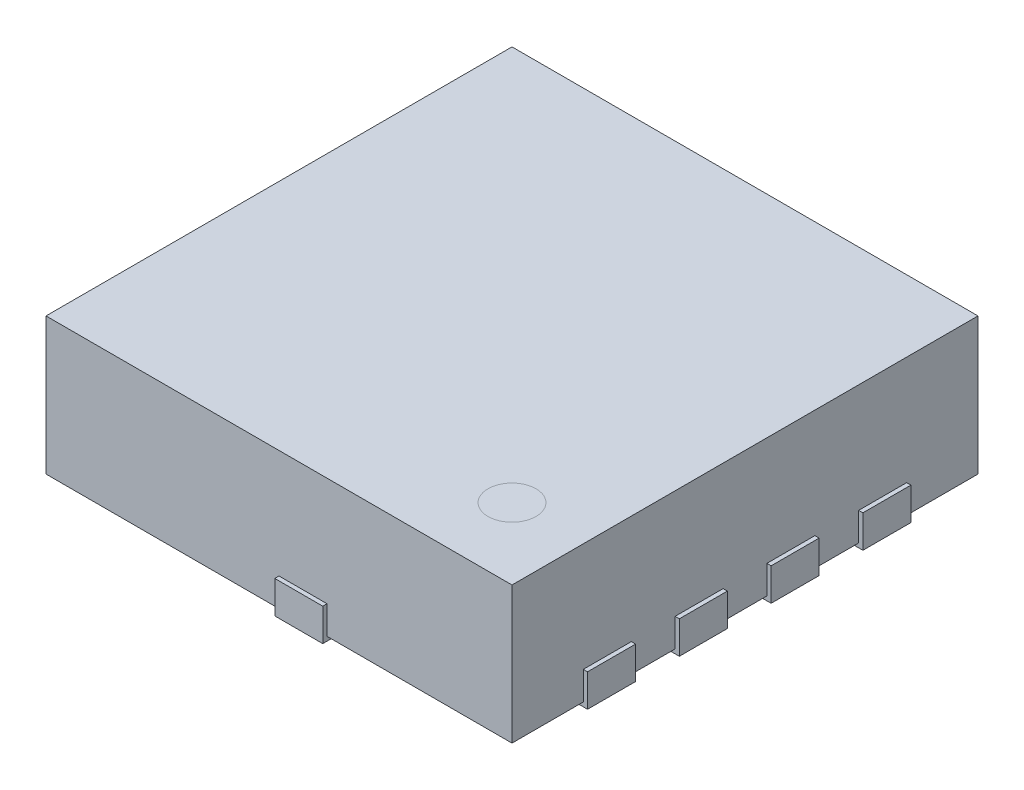
SolidWorks part; units mm, degrees
ref_plane "Спереди" through (0, 0, 0) normal (0, 0, 1) x (1, 0, 0)
ref_plane "Сверху" through (0, 0, 0) normal (0, 1, 0) x (1, 0, 0)
ref_plane "Справа" through (0, 0, 0) normal (1, 0, 0) x (0, 0, -1)
sketch "Эскиз1" plane through (0, 0, 0) normal (0, 1, 0) x (1, 0, 0)
  line L1 (-1.65, -1.65) -> (1.65, -1.65)
  line L2 (-1.65, -1.65) -> (-1.65, 1.65)
  line L3 (-1.65, 1.65) -> (1.65, 1.65)
  line L4 (1.65, -1.65) -> (1.65, 1.65)
  line L5 (-1.65, -1.65) -> (1.65, 1.65) construction
  line L6 (-1.65, 1.65) -> (1.65, -1.65) construction
  point P0 (0, 0)
  dimension "D1" = 3.3
  dimension "D2" = 3.3
extrude "Бобышка-Вытянуть1" add sketch "Эскиз1" along normal blind 0.97 from offset 0.03
sketch "Эскиз2" plane through (0, 0, 0) normal (0, 1, 0) x (1, 0, 0)
  line L0 (0, 0) -> (2.6746, 0) construction
  line L1 (0, 0) -> (0, 2.2255) construction
  line L2 (-0.2068, 0.325) -> (2.6483, 0.325) construction
  line L3 (-0.6239, 0.975) -> (2.6483, 0.975) construction
  line L4 (-0.6239, -0.975) -> (2.6483, -0.975) construction
  line L5 (-0.2068, -0.325) -> (2.6483, -0.325) construction
  line L7 (1.2, 0.805) -> (1.68, 0.805)
  line L8 (1.2, 0.805) -> (1.2, 1.145)
  line L9 (1.2, 1.145) -> (1.68, 1.145)
  line L10 (1.68, 0.805) -> (1.68, 1.145)
  line L11 (1.2, 0.805) -> (1.68, 1.145) construction
  line L12 (1.2, 1.145) -> (1.68, 0.805) construction
  line L13 (1.2, 0.495) -> (1.68, 0.495)
  line L14 (1.2, 0.155) -> (1.2, 0.495)
  line L15 (1.2, 0.155) -> (1.68, 0.155)
  line L16 (1.68, 0.155) -> (1.68, 0.495)
  line L17 (1.2, -0.155) -> (1.68, -0.155)
  line L18 (1.2, -0.495) -> (1.2, -0.155)
  line L19 (1.2, -0.495) -> (1.68, -0.495)
  line L20 (1.68, -0.495) -> (1.68, -0.155)
  line L21 (1.2, -0.805) -> (1.68, -0.805)
  line L22 (1.2, -1.145) -> (1.2, -0.805)
  line L23 (1.2, -1.145) -> (1.68, -1.145)
  line L24 (1.68, -1.145) -> (1.68, -0.805)
  line L25 (1.68, 0.805) -> (1.68, -1.145)
  line L26 (1.68, 0) -> (1.68, 2.2341) construction
  line L27 (1.65, -1.65) -> (1.65, 1.65) construction
  point P12 (1.44, 0.975)
  dimension "D1" = 0.325
  dimension "D2" = 0.65
  dimension "D3" = 0.34
  dimension "D4" = 0.48
  dimension "D6" = 0.65
  dimension "D7" = 0.03
  dimension "D5" = 4
extrude "Бобышка-Вытянуть2" add sketch "Эскиз2" along normal blind 0.23 separate body contours L23 L24 L21 L22 | L15 L16 L13 L14 | L7 L10 L9 L8 | L19 L20 L17 L18 region at (1.44, 0, -0.975) region at (1.44, 0, 0.975) region at (1.44, 0, -0.325)
sketch "Эскиз3" plane through (0, 0, 0) normal (0, 1, 0) x (1, 0, 0)
  line L0 (0, 0) -> (2.6746, 0) construction
  line L1 (0, 0) -> (0, 2.2255) construction
  line L2 (-0.2068, 0.325) -> (2.6483, 0.325) construction
  line L3 (-0.6239, 0.975) -> (2.6483, 0.975) construction
  line L4 (-0.6239, -0.975) -> (2.6483, -0.975) construction
  line L5 (-0.2068, -0.325) -> (2.6483, -0.325) construction
  line L6 (1.65, -1.65) -> (1.65, 1.65) construction
  line L7 (1.2, 0.805) -> (1.68, 0.805) construction
  line L8 (1.2, 0.805) -> (1.2, 1.145) construction
  line L9 (1.2, 1.145) -> (1.68, 1.145) construction
  line L10 (1.68, 0.805) -> (1.68, 1.145) construction
  line L11 (1.2, 0.805) -> (1.68, 1.145) construction
  line L12 (1.2, 1.145) -> (1.68, 0.805) construction
  line L13 (1.2, 0.495) -> (1.68, 0.495) construction
  line L14 (1.2, 0.155) -> (1.2, 0.495) construction
  line L15 (1.2, 0.155) -> (1.68, 0.155) construction
  line L16 (1.68, 0.155) -> (1.68, 0.495) construction
  line L17 (1.2, -0.155) -> (1.68, -0.155) construction
  line L18 (1.2, -0.495) -> (1.2, -0.155) construction
  line L19 (1.2, -0.495) -> (1.68, -0.495) construction
  line L20 (1.68, -0.495) -> (1.68, -0.155) construction
  line L21 (1.2, -0.805) -> (1.68, -0.805) construction
  line L22 (1.2, -1.145) -> (1.2, -0.805) construction
  line L23 (1.2, -1.145) -> (1.68, -1.145) construction
  line L24 (1.68, -1.145) -> (1.68, -0.805) construction
  line L25 (1.68, 0.805) -> (1.68, -1.145) construction
  line L26 (1.68, 0) -> (1.68, 2.2341) construction
  line L27 (-1.2, -1.145) -> (-1.2, -1.225)
  line L28 (-1.2, -1.145) -> (-1.68, -1.145)
  line L29 (-1.68, -1.145) -> (-1.68, -0.805)
  line L30 (-1.2, -0.805) -> (-1.68, -0.805)
  line L31 (-1.2, -0.495) -> (-1.68, -0.495)
  line L32 (-1.68, -0.495) -> (-1.68, -0.155)
  line L33 (-1.2, -0.155) -> (-1.68, -0.155)
  line L34 (-1.2, 0.155) -> (-1.68, 0.155)
  line L35 (-1.68, 0.155) -> (-1.68, 0.495)
  line L36 (-1.2, 0.495) -> (-1.68, 0.495)
  line L37 (-1.68, 0.805) -> (-1.68, 1.145)
  line L38 (-1.2, 0.805) -> (-1.68, 0.805)
  line L39 (-1.2, 1.145) -> (-1.68, 1.145)
  line L40 (-1.2, 1.145) -> (-1.2, 1.225)
  line L41 (-1.2, 1.225) -> (1.1032, 1.225) construction
  line L42 (-1.2, -1.225) -> (1.3591, -1.225) construction
  line L43 (-1.2, 0.805) -> (-1.2, 0.495)
  line L44 (-1.2, 0.155) -> (-1.2, -0.155)
  line L45 (-1.2, -0.495) -> (-1.2, -0.805)
  line L46 (0.55, 2.3245) -> (0.55, -2.1968) construction
  line L48 (-1.65, 1.65) -> (-1.65, -1.65) construction
  line L49 (1.65, 1.65) -> (-1.65, 1.65) construction
  line L50 (0, 1.225) -> (0.34, 1.225) construction
  line L51 (0, 1.225) -> (0, 1.68)
  line L52 (0, 1.68) -> (0.34, 1.68)
  line L53 (0.34, 1.225) -> (0.34, 1.68)
  line L54 (-1.2, 1.225) -> (0, 1.225)
  line L55 (0.34, 1.225) -> (0.55, 1.225)
  line L56 (-1.2, -1.225) -> (0, -1.225)
  line L57 (0, -1.225) -> (0, -1.68)
  line L58 (0, -1.68) -> (0.34, -1.68)
  line L59 (0.34, -1.225) -> (0.34, -1.68)
  line L60 (0.34, -1.225) -> (0.55, -1.225)
  line L61 (0.55, 1.225) -> (0.55, -1.225)
  point P12 (1.44, 0.975)
  dimension "D1" = 0.325
  dimension "D2" = 0.65
  dimension "D3" = 0.34
  dimension "D4" = 0.48
  dimension "D6" = 0.65
  dimension "D7" = 0.03
  dimension "D8" = 2.45
  dimension "D9" = 1.75
  dimension "D10" = 0.45
  dimension "D11" = 0.34
  dimension "D12" = 0.03
  dimension "D13" = 0.425
  dimension "D5" = 4
extrude "Бобышка-Вытянуть3" add sketch "Эскиз3" along normal blind 0.23 separate body
sketch "Эскиз4" plane through (0, 0, 0) normal (0, 1, 0) x (1, 0, 0)
  line L0 (1.68, -1.145) -> (-0.3544, -1.145) construction
  line L1 (-1.65, -1.65) -> (1.65, -1.65) construction
  line L2 (1.65, -1.65) -> (1.65, 1.65) construction
  circle A0 centre (1.145, -1.145) radius 0.17
  dimension "D3" = 0.34
  dimension "D1" = 0.505
  dimension "D2" = 0.505
extrude "Вырез-Вытянуть1" cut sketch "Эскиз4" against normal blind 0.03 from offset 1
extrude "Бобышка-Вытянуть4" add sketch "Эскиз4<2>" against normal blind 0.03 from offset 1 separate body
sketch "Эскиз4<2>" plane through (0, 0, 0) normal (0, 1, 0) x (1, 0, 0) same geometry as "Эскиз4"
